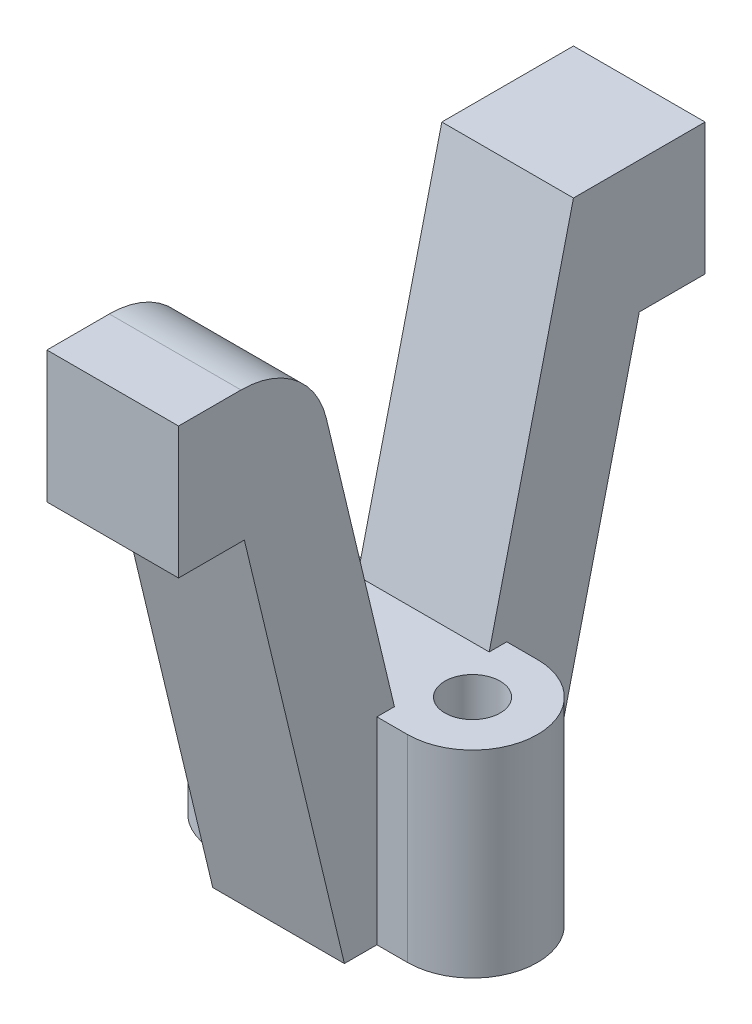
SolidWorks part; units mm, degrees
ref_plane "Front Plane" through (0, 0, 0) normal (0, 0, 1) x (1, 0, 0)
ref_plane "Top Plane" through (0, 0, 0) normal (0, 1, 0) x (1, 0, 0)
ref_plane "Right Plane" through (0, 0, 0) normal (1, 0, 0) x (0, 0, -1)
sketch "Sketch2" plane through (0, 0, 0) normal (1, 0, 0) x (0, 0, -1)
  line L0 (-6, 12.5) -> (-6, 9.5)
  line L1 (-6, 12.5) -> (0, 12.5) construction
  line L2 (-6, 9.5) -> (-4.5, 9.5)
  line L3 (-6, 12.5) -> (-3, 12.5)
  line L4 (-3, 12.5) -> (0, 0)
  line L5 (0, 0) -> (-2.22, 0)
  line L6 (-2.22, 0) -> (-4.5, 9.5)
  dimension "D1" = 6
  dimension "D2" = 3
  dimension "D3" = 1.5
  dimension "D4" = 3
  dimension "D5" = 12.5
extrude "Boss-Extrude2" add sketch "Sketch2" along normal blind 1.5 and the other way blind 1.5
fillet "Fillet1" radius 2 1 edges at (0, 12.5, 3)
sketch "Sketch1" plane through (0, 0, 0) normal (0, 1, 0) x (1, 0, 0)
  line L0 (-2.2, 0) -> (2.2, 0) construction
  line L1 (-2.2, 0) -> (2.2, 0) construction
  line L2 (-2.2, 1.48) -> (2.2, 1.48)
  line L3 (-2.2, -1.48) -> (2.2, -1.48)
  line L4 (0, 0) -> (0, -6) construction
  circle A0 centre (-2.2, 0) radius 0.63
  circle A1 centre (2.2, 0) radius 0.63
  arc A2 (-2.2, 1.48) -> (-2.2, -1.48) centre (-2.2, 0) ccw
  arc A3 (2.2, -1.48) -> (2.2, 1.48) centre (2.2, 0) ccw
  point P4 (0, 0)
  point P7 (0, 0)
  dimension "D2" = 1.26
  dimension "D3" = 1.48
  dimension "D1" = 4.4
  dimension "D4" = 6
extrude "Boss-Extrude3" add sketch "Sketch1" along normal blind 4.5
mirror "Mirror1" about plane through (0, 0, 0) normal (0, 0, 1) of "Boss-Extrude2"
equation "\"TubingOD\"= 1.26"
equation "\"ConcentricDepth\"= 4.5mm"
equation "\"D2@Sketch1\"=\"TubingOD\""
equation "\"D1@Boss-Extrude3\"=\"ConcentricDepth\""
